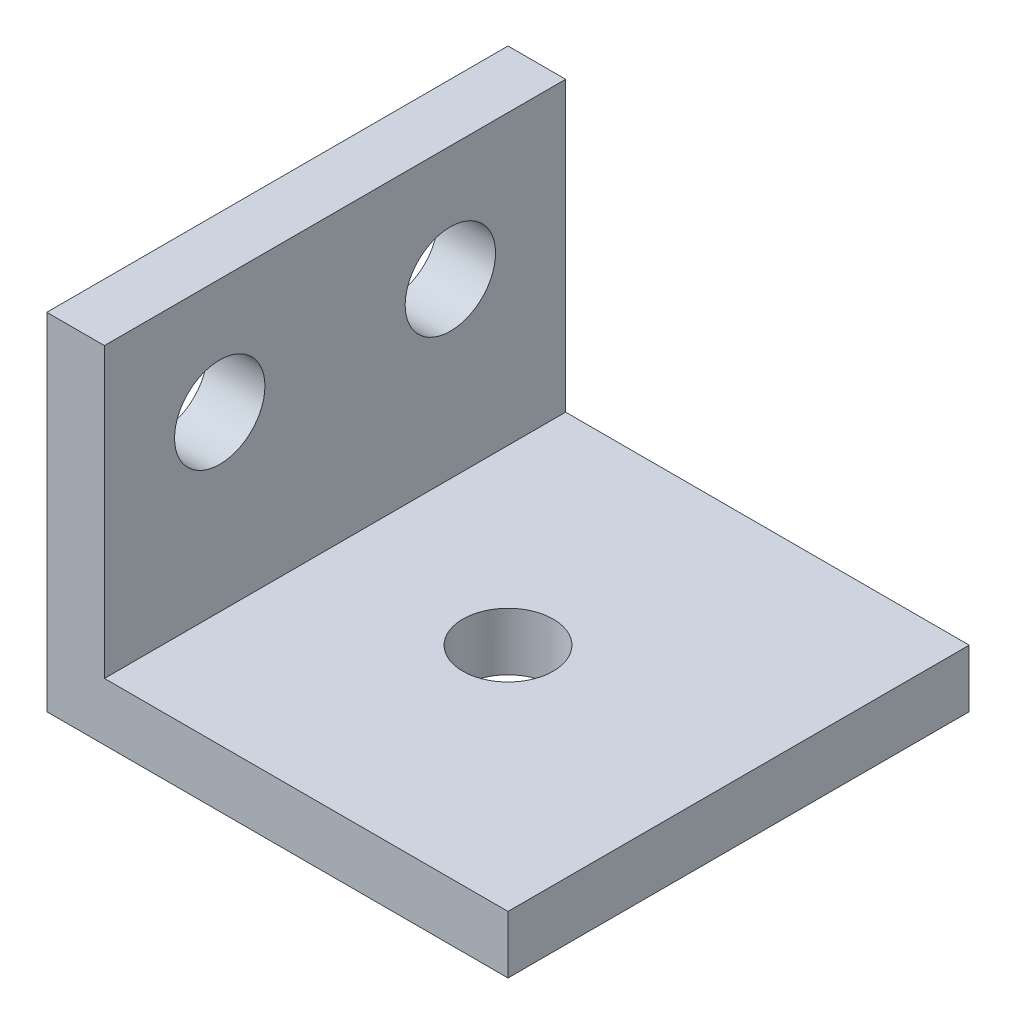
SolidWorks part; units mm, degrees
ref_plane "Front Plane" through (0, 0, 0) normal (0, 0, 1) x (1, 0, 0)
ref_plane "Top Plane" through (0, 0, 0) normal (0, 1, 0) x (1, 0, 0)
ref_plane "Right Plane" through (0, 0, 0) normal (1, 0, 0) x (0, 0, -1)
sketch "Sketch1" plane through (0, 0, 0) normal (0, 0, 1) x (1, 0, 0)
  line L0 (0, 0) -> (0, 19.05)
  line L1 (0, 19.05) -> (3.175, 19.05)
  line L2 (3.175, 19.05) -> (3.175, 3.175)
  line L3 (3.175, 3.175) -> (25.4, 3.175)
  line L4 (25.4, 3.175) -> (25.4, 0)
  line L5 (25.4, 0) -> (0, 0)
  dimension "D1" = 3.175
  dimension "D2" = 19.05
  dimension "D3" = 25.4
extrude "Boss-Extrude1" add sketch "Sketch1" along normal mid plane 25.4
sketch "Sketch3" plane through (0, 3.175, 0) normal (0, 1, 0) x (1, 0, 0)
  line L0 (0, -12.7) -> (25.4, -12.7) construction
  line L1 (25.4, -12.7) -> (25.4, 12.7) construction
  circle A0 centre (12.7, 0) radius 2.4892
  point P4 (12.7, -12.7)
  point P7 (25.4, 0)
  dimension "D1" = 4.9784
extrude "Cut-Extrude1" cut sketch "Sketch3" against normal through all both and the other way through all
sketch "Sketch4" plane through (3.175, 0, 0) normal (1, 0, 0) x (0, 0, -1)
  line L0 (12.7, 3.175) -> (12.7, 19.05) construction
  line L2 (-12.7, 19.05) -> (12.7, 19.05) construction
  circle A0 centre (-6.35, 12.7) radius 2.4892
  circle A1 centre (6.35, 12.7) radius 2.4892
  point P9 (0, 0)
  dimension "D1" = 4.9784
  dimension "D2" = 6.35
  dimension "D3" = 12.7
  dimension "D4" = 6.35
extrude "Cut-Extrude2" cut sketch "Sketch4" against normal through all both and the other way through all
